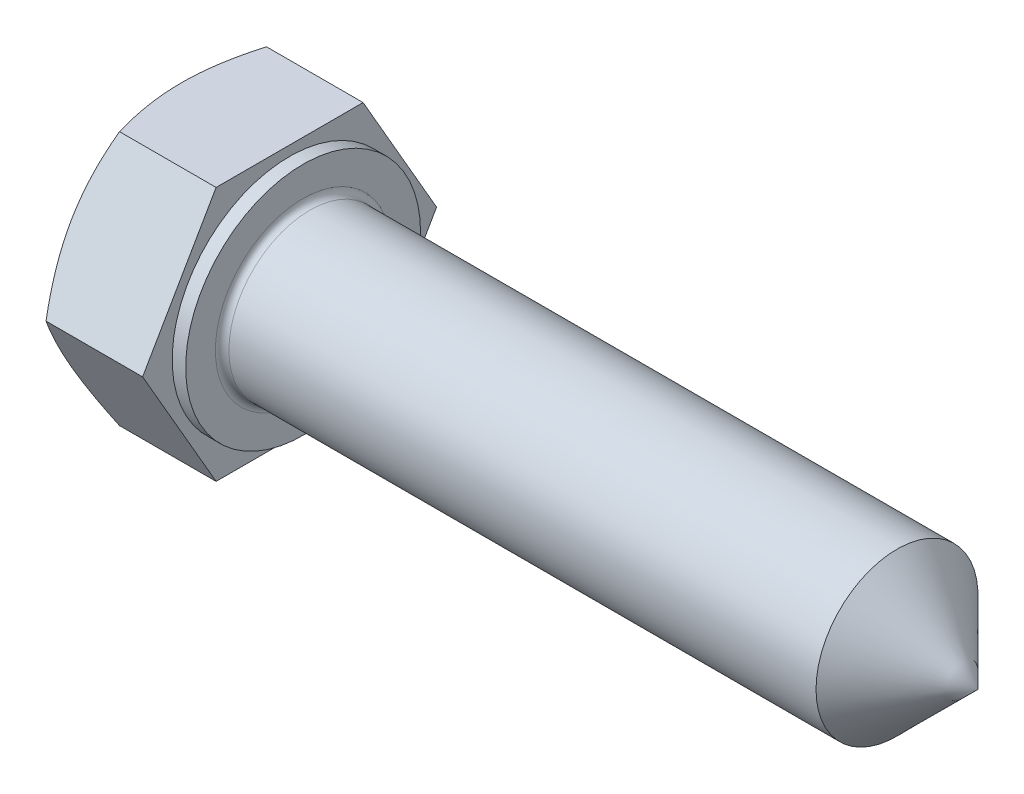
SolidWorks part; units mm, degrees
ref_plane "Front" through (0, 0, 0) normal (0, 0, 1) x (1, 0, 0)
ref_plane "Top" through (0, 0, 0) normal (0, 1, 0) x (1, 0, 0)
ref_plane "Right" through (0, 0, 0) normal (1, 0, 0) x (0, 0, -1)
sketch "Sketch3" plane through (0, 0, 0) normal (1, 0, 0) x (0, 0, -1)
  line L1 (-5.445, 0) -> (-2.7225, -4.7155)
  line L2 (-2.7225, -4.7155) -> (2.7225, -4.7155)
  line L3 (2.7225, -4.7155) -> (5.445, 0)
  line L4 (5.445, 0) -> (2.7225, 4.7155)
  line L5 (2.7225, 4.7155) -> (-2.7225, 4.7155)
  line L6 (-2.7225, 4.7155) -> (-5.445, 0)
  circle A0 centre (0, 0) radius 4.7155 construction
  dimension "e" = 10.89
extrude "BaseHead" add sketch "Sketch3" along normal blind 4
sketch "Sketch2" plane through (4, -1.7393, 0.8693) normal (1, 0, 0) x (0, 0, -1)
  circle A0 centre (0.8693, 1.7393) radius 4.35
  dimension "dw" = 8.7
extrude "Neck" add sketch "Sketch2" along normal blind 0.5
sketch "Sketch1" plane through (4.5, -1.8832, 0.2627) normal (1, 0, 0) x (0, 0, -1)
  circle A0 centre (0.2627, 1.8832) radius 3
extrude "BaseBody" add sketch "Sketch1" along normal blind 25
cosmetic thread "ThreadCosmetic1" [suppressed] parameters "D1"=20, "dm"=4.5
sketch "Sketch4" plane through (6.9064, 0, -1.4614) normal (0, 1, 0) x (0, 0, -1)
  line L0 (3.9836, 2.9064) -> (3.9836, 6.9064) construction
  line L1 (3.9836, 6.9064) -> (3.9836, 6.4852)
  line L3 (3.2541, 6.9064) -> (3.9836, 6.9064)
  line L4 (-1.4614, -0.8876) -> (-1.4614, 9.2553) construction
  line L6 (3.2541, 6.9064) -> (3.9836, 6.4852)
  line L7 (3.9836, 6.9064) -> (1.2611, 6.9064) construction
  dimension "D2" = 30
revolve "Cut-Revolve1" cut sketch "Sketch4" angle 360 about L4
sketch "Sketch6" plane through (-10.5798, 0, 31.5798) normal (0, 1, 0) x (0, 0, -1)
  line L0 (31.5798, -1.5701) -> (31.5798, -40.5895) construction
  line L2 (31.5798, -43.0146) -> (52.5798, -43.0146)
  line L3 (52.5798, -43.0146) -> (52.5798, -19.0798)
  line L4 (52.5798, -19.0798) -> (31.5798, -40.0798)
  line L5 (31.5798, -40.0798) -> (31.5798, -43.0146)
  line L6 (28.5798, -40.0798) -> (34.5798, -40.0798) construction
  dimension "D1" = 45
  dimension "D2" = 21
  dimension "D3" = 2.9348
revolve "Cut-Revolve2" cut sketch "Sketch6" angle 360 about L0
fillet "Fillet1" radius 0.25 1 edges at (4.5, 0, -3)
sketch "Sketch7" plane through (0, 0, 0) normal (0, 0, 1) x (1, 0, 0)
  line L0 (6.5, 3.2) -> (7.25, 3.2)
  line L1 (7.25, 3.2) -> (7.25, 3)
  line L2 (7.25, 3) -> (6.875, 2.3505)
  line L3 (6.5, 3) -> (6.875, 2.3505)
  line L4 (6.5, 3.2) -> (6.5, 3)
  line L5 (10.7743, 0) -> (0, 0) construction
  line L6 (6.5, 3) -> (7.25, 3) construction
  line L7 (6.875, 3) -> (6.875, 2.3505) construction
  line L8 (26.5, 3) -> (4.75, 3) construction
  point P5 (6.875, 3.2)
  dimension "D3" = 23
revolve "Cut-Revolve10" [suppressed] cut sketch "Sketch7" angle 360 about L5
pattern_linear "LPattern10" [suppressed] count 15 spacing 1.5 of bodies 108
equation "\"D2@Sketch7\" = (  \"d@Sketch1\" - \"dm@ThreadCosmetic1\" )  / 2"
equation "\"D3@Sketch7\" = \"D1@ThreadCosmetic1\" + \"d@Sketch1\" / 2"
equation "\"D3@LPattern10\" = \"D2@Sketch7\" * 2"
equation "\"D1@LPattern10\" = \"D3@Sketch7\" / \"D3@LPattern10\""
